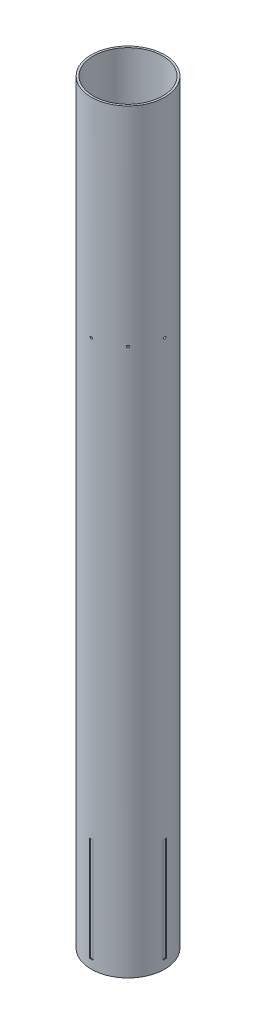
SolidWorks part; units mm, degrees
material "Hexcel AS4C (3000 Filaments)"
ref_plane "Front Plane" through (0, 0, 0) normal (0, 0, 1) x (1, 0, 0)
ref_plane "Top Plane" through (0, 0, 0) normal (0, 1, 0) x (1, 0, 0)
ref_plane "Right Plane" through (0, 0, 0) normal (1, 0, 0) x (0, 0, -1)
sketch "Sketch1" plane through (0, 0, 0) normal (0, 1, 0) x (1, 0, 0)
  circle A0 centre (0, 0) radius 50.8
  dimension "D1" = 101.6
extrude "Body Tube Extrusion" add sketch "Sketch1" along normal blind 1104.9 thin thin type one direction wall 2.921
ref_plane "Plane1" through (0, 0, 53.721) normal (0, 0, 1) x (1, 0, 0)
sketch "Sketch2" plane through (0, 0, 53.721) normal (0, 0, 1) x (1, 0, 0)
  line L0 (0, 1104.9) -> (0, 0) construction
  line L1 (50.8, 1104.9) -> (-50.8, 1104.9) construction
  line L2 (-53.721, 0) -> (53.721, 0) construction
  circle A0 centre (0, 800.1) radius 1.6383
  dimension "D1" = 3.2766
  dimension "D2" = 800.1
extrude "Bulkhead Hole" cut sketch "Sketch2" against normal up to next
pattern_circular "CirPattern1" count 8 over 360 about axis through (0, 1104.9, 0) along (0, -1, 0) of "Bulkhead Hole"
sketch "Sketch3" plane through (0, 0, 53.721) normal (0, 0, 1) x (1, 0, 0)
  line L0 (0, 0) -> (0, 12.7) construction
  line L1 (-50.8, 0) -> (50.8, 0) construction
  line L2 (0, 1104.9) -> (0, 0) construction
  line L4 (-2.667, 165.1) -> (2.667, 165.1)
  line L5 (-2.667, 165.1) -> (-2.667, 12.7)
  line L6 (-2.667, 12.7) -> (2.667, 12.7)
  line L7 (2.667, 165.1) -> (2.667, 12.7)
  point P10 (0, 12.7)
  dimension "D1" = 152.4
  dimension "D2" = 5.334
  dimension "D3" = 12.7
extrude "Cut-Extrude1" cut sketch "Sketch3" against normal blind 1.27
pattern_circular "CirPattern2" count 4 over 360 about axis through (0, 1104.9, 0) along (0, -1, 0) of "Cut-Extrude1" reverse direction yes
